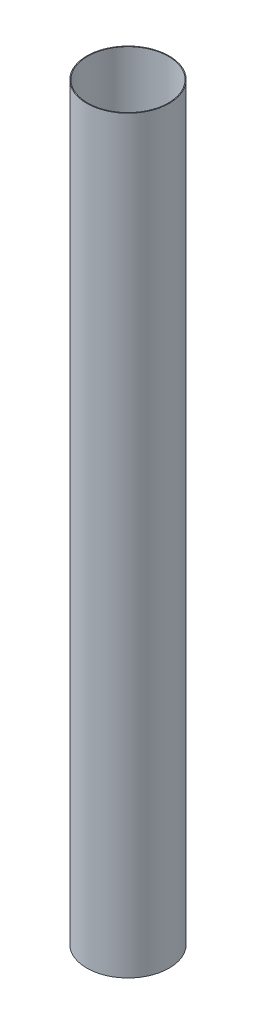
SolidWorks part; units mm, degrees
material "ПВХ 0.007 Смягченный"
ref_plane "Спереди" through (0, 0, 0) normal (0, 0, 1) x (1, 0, 0)
ref_plane "Сверху" through (0, 0, 0) normal (0, 1, 0) x (1, 0, 0)
ref_plane "Справа" through (0, 0, 0) normal (1, 0, 0) x (0, 0, -1)
sketch "Эскиз1" plane through (0, 0, 0) normal (0, 1, 0) x (1, 0, 0)
  circle A0 centre (0, 0) radius 55
  circle A1 centre (0, 0) radius 54
  dimension "ExDBody" = 110
  dimension "InDBody" = 108
extrude "Бобышка-Вытянуть1" add sketch "Эскиз1" along normal blind 1000
